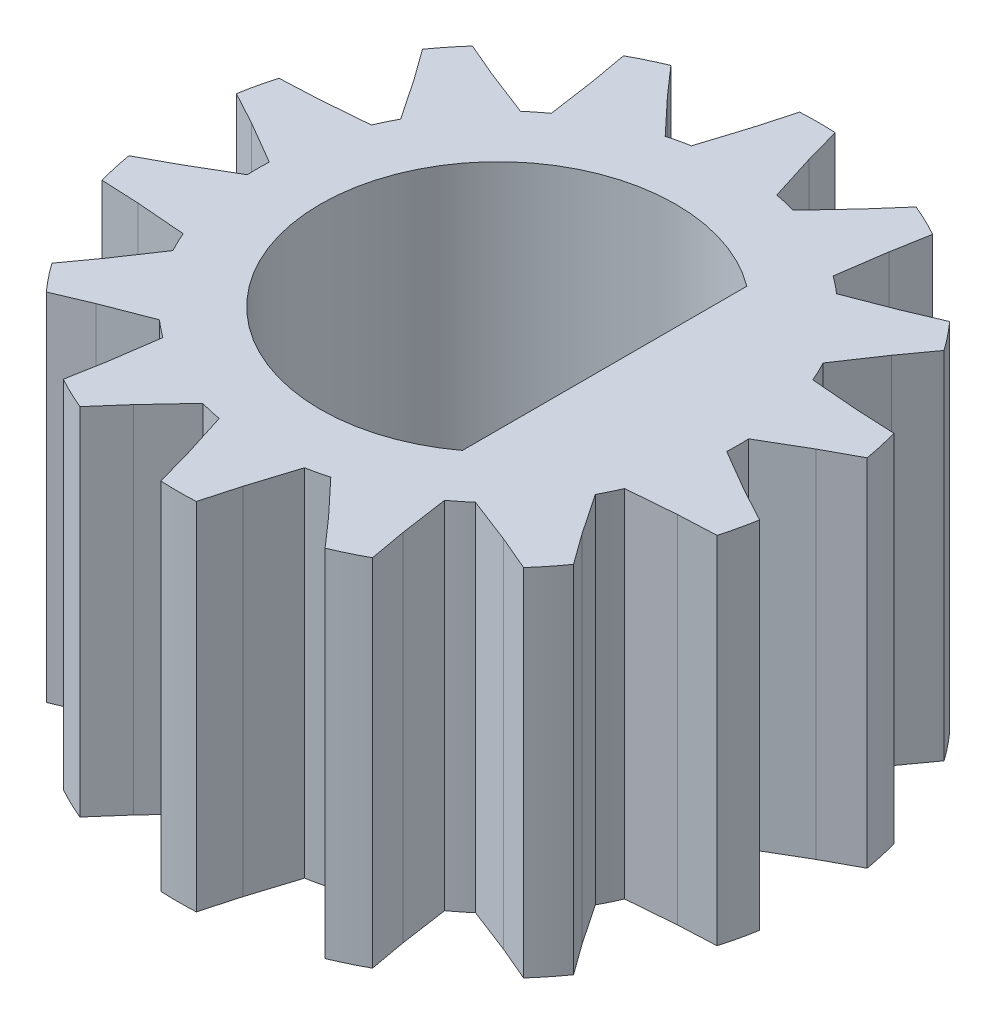
SolidWorks part; units mm, degrees
ref_plane "Front Plane" through (0, 0, 0) normal (0, 0, 1) x (1, 0, 0)
ref_plane "Top Plane" through (0, 0, 0) normal (0, 1, 0) x (1, 0, 0)
ref_plane "Right Plane" through (0, 0, 0) normal (1, 0, 0) x (0, 0, -1)
sketch "Sketch2" plane through (0, 0, 0) normal (0, 1, 0) x (1, 0, 0)
  line L0 (0, -6.964) -> (0, 6.964) construction
  line L1 (-0.6, 3.3212) -> (-0.3925, 3.9807)
  line L2 (0.6, 3.3212) -> (0.3925, 3.9807)
  line L3 (0.3925, 3.9807) -> (0.25, 4.4931)
  line L4 (-0.3925, 3.9807) -> (-0.25, 4.4931)
  line L5 (1.5, 2) -> (1.5, -2)
  circle A0 centre (0, 0) radius 4.5
  circle A1 centre (0, 0) radius 4 construction
  circle A2 centre (0, 0) radius 3.375
  arc A3 (1.5, 2) -> (1.5, -2) centre (0, 0) ccw
  point P5 (0, 4)
  point P8 (0, 0)
  point P9 (0, 4.5)
  point P10 (0, 3.375)
  point P15 (0.3925, 3.9807)
  point P16 (-0.3925, 3.9807)
  dimension "D1" = 9
  dimension "D2" = 6.75
  dimension "D3" = 8
  dimension "D10" = 5
  dimension "D4" = 0.3925
  dimension "D5" = 0.3925
  dimension "D6" = 0
  dimension "D7" = 0.6
  dimension "D8" = 0.6
  dimension "D9" = 0.25
  dimension "D11" = 4
extrude "Boss-Extrude1" add sketch "Sketch2" along normal blind 5 contours A2 | L2 L1 A2 region at (0, 0, -3.8491) region at (0, 0, -3.2795)
sketch "Sketch3" plane through (0, 0, 0) normal (1, 0, 0) x (0, 0, -1)
  line L0 (0, -15.4623) -> (0, 15.4623) construction
  point P4 (0, 0)
pattern_circular "CirPattern1" count 14 over 360 about axis through (0, 5, 0) along (0, 1, 0) of face at (0.3212, 2.5, -4.2369) of face at (0.4962, 2.5, -3.651) of face at (0, 2.5, -4.4965) of face at (-0.3213, 2.5, -4.2369) of face at (-0.4963, 2.5, -3.651)
